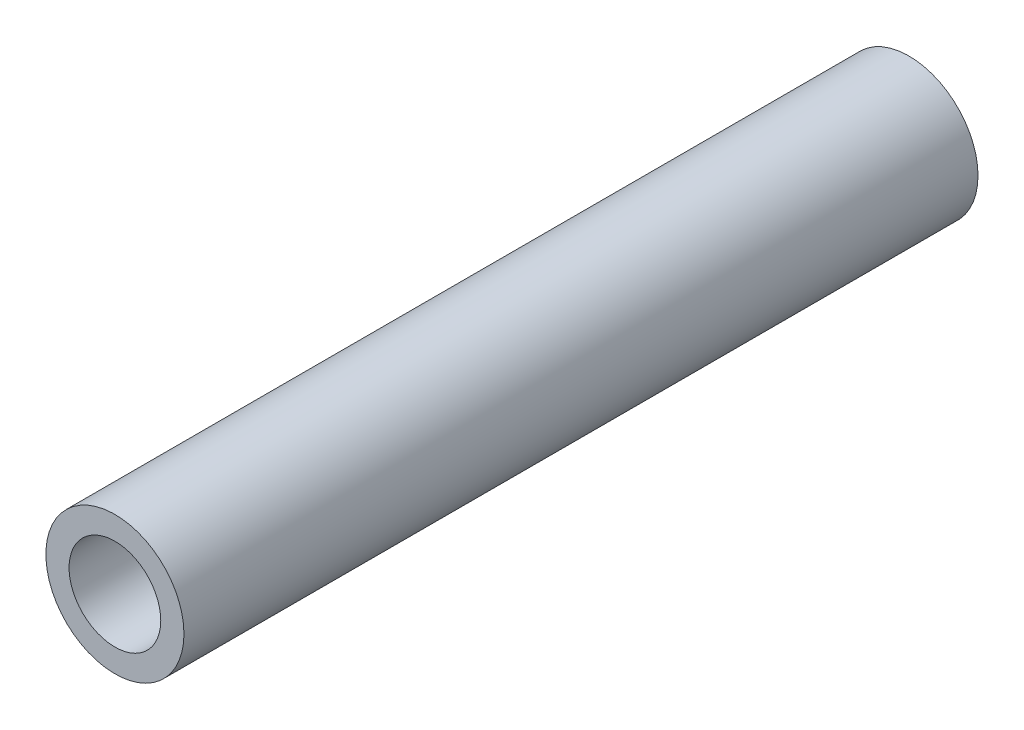
SolidWorks part; units mm, degrees
ref_plane "Front Plane" through (0, 0, 0) normal (0, 0, 1) x (1, 0, 0)
ref_plane "Top Plane" through (0, 0, 0) normal (0, 1, 0) x (1, 0, 0)
ref_plane "Right Plane" through (0, 0, 0) normal (1, 0, 0) x (0, 0, -1)
sketch "Sketch1" plane through (0, 0, 0) normal (1, 0, 0) x (0, 0, -1)
  line L0 (-18.2562, -2.1082) -> (-18.2562, 2.1082) construction
  line L1 (18.2562, -3.175) -> (-18.2562, -3.175) construction
  line L2 (18.2562, -3.175) -> (18.2562, 3.175) construction
  line L3 (18.2562, 3.175) -> (-18.2562, 3.175) construction
  line L4 (-18.2562, -3.175) -> (-18.2562, 3.175) construction
  line L5 (0, 3.175) -> (0, -3.175) construction
  line L6 (18.2562, 0) -> (-18.2562, 0) construction
  point P0 (0, 0)
  point P7 (-18.2562, 0)
  dimension "D1" = 4.2164
  dimension "D2" = 6.35
sketch "Sketch3" plane through (0, 0, 0) normal (0, 0, 1) x (1, 0, 0)
  circle A0 centre (0, 0) radius 2.1082 construction
  circle A1 centre (0, 0) radius 3.175 construction
  point P6 (0, -2.1082)
  dimension "OD" = 6.35
  dimension "ID" = 4.2164
sketch "Sketch2" plane through (0, 0, 0) normal (0, 0, 1) x (1, 0, 0)
  circle A0 centre (0, 0) radius 3.175
  circle A1 centre (0, 0) radius 2.1082
extrude "Extrude1" add sketch "Sketch2" along normal up to vertex and the other way up to vertex up to point (0, -3.175, 18.2562) other way up to point (0, 3.175, -18.2562)
equation "\"D1@Sketch1\"=\"ID@Sketch3\""
equation "\"D2@Sketch1\"=\"OD@Sketch3\""
